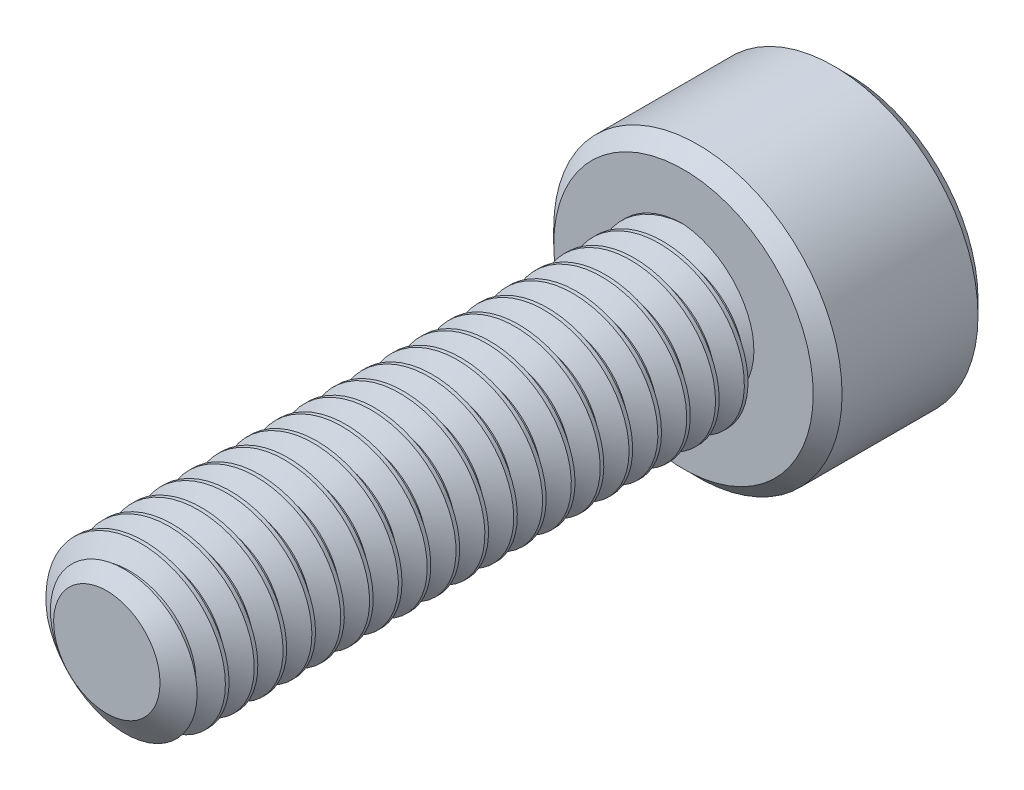
SolidWorks part; units mm, degrees
other "DetailItem1"
ref_plane "Front Plane" through (0, 0, 0) normal (0, 0, 1) x (1, 0, 0)
ref_plane "Top Plane" through (0, 0, 0) normal (0, 1, 0) x (1, 0, 0)
ref_plane "Right Plane" through (0, 0, 0) normal (1, 0, 0) x (0, 0, -1)
sketch "Sketch1" plane through (0, 0, 0) normal (0, 0, 1) x (1, 0, 0)
  circle A0 centre (0, 0) radius 2
  dimension "OD" = 4
extrude "Extrude1" add sketch "Sketch1" against normal blind 14
sketch "Sketch2" plane through (0, 0, 0) normal (0, 0, 1) x (1, 0, 0)
  circle A0 centre (0, 0) radius 2 construction
  circle A1 centre (0, 0) radius 2
curve "Helix/Spiral1" pitch 0.7 height 14.7 radius 2 centre (0, 0, 0) axis (0, 0, -1) start towards (0, 1, 0) parameters "pitch"=0.7
sketch "Sketch3" plane through (0, 0, 0) normal (1, 0, 0) x (0, 0, -1)
  line L0 (-0.6125, 2) -> (-0.35, 1.5453)
  line L1 (-0.35, 1.5453) -> (-0.2625, 1.5453)
  line L2 (-0.2625, 1.5453) -> (0, 2)
  line L3 (-0.6125, 2) -> (0, 2)
  line L4 (-0.3062, 2) -> (-0.3062, 1.5453) construction
  line L5 (-0.4812, 1.7727) -> (-0.1312, 1.7727) construction
  line L6 (0, 2) -> (0, -2) construction
  dimension "D1" = 0.0875
  dimension "D2" = 0.35
  dimension "D3" = 60
sweep "Cut-Sweep1" cut profiles "Sketch3" path "Helix/Spiral1" align with end faces yes
sketch "Sketch4" plane through (0, 0, 0) normal (1, 0, 0) x (0, 0, -1)
  line L0 (0.4962, 2) -> (0, 1.2913)
  line L1 (0, 1.2913) -> (0, 2)
  line L2 (0.4962, 2) -> (0, 2)
  line L3 (-0.6125, 2) -> (0, 2) construction
  line L4 (0, 0) -> (7.0209, 0) construction
  dimension "D1" = 55
  dimension "D2" = 0.254
revolve "Cut-Revolve1" cut sketch "Sketch4" angle 360 about L4
sketch "Sketch6" plane through (0, 0, -14) normal (0, 0, -1) x (-1, 0, 0)
  circle A0 centre (0, 0) radius 3.5
  dimension "head dia" = 7
extrude "Extrude2" add sketch "Sketch6" along normal blind 4
sketch "Sketch7" plane through (0, 0, -18) normal (0, 0, -1) x (-1, 0, 0)
  line L1 (0, 1.7321) -> (-1.5, 0.866)
  line L2 (-1.5, 0.866) -> (-1.5, -0.866)
  line L3 (-1.5, -0.866) -> (0, -1.7321)
  line L4 (0, -1.7321) -> (1.5, -0.866)
  line L5 (1.5, -0.866) -> (1.5, 0.866)
  line L6 (1.5, 0.866) -> (0, 1.7321)
  circle A0 centre (0, 0) radius 1.5 construction
  dimension "hex dia" = 3
extrude "Cut-Extrude1" cut sketch "Sketch7" against normal blind 2.25
sketch "Sketch8" plane through (0, 0, -18) normal (0, 0, -1) x (-1, 0, 0)
  circle A0 centre (0, 0) radius 1.7321
extrude "Cut-Extrude2" cut sketch "Sketch8" against normal through all draft 45
chamfer "Chamfer1" distance 0.35 angle 45 2 edges at (-3.5, 0, -18) (-3.5, 0, -14)
sketch "Sketch10" plane through (0, 0, -14) normal (0, 0, 1) x (1, 0, 0)
  circle A1 centre (0, 0) radius 2
  circle A2 centre (0, 0) radius 2
  dimension "D1" = 0
ref_plane "Plane1" through (0, 0, -22) normal (0, 0, 1) x (1, 0, 0)
extrude "partial thread" [suppressed] add sketch "Sketch10" along normal up to surface (58 mm away) separate body up to plane "Plane1"
chamfer "Chamfer2" [suppressed] distance 0.08 angle 45
combine bodies "Combine1" [suppressed] operation type add bodies to combine 107 108
sketch "Sketch9" plane through (0, 0, 0) normal (1, 0, 0) x (0, 0, -1)
  line L0 (0, 2) -> (0, -2) construction
  line L1 (1.75, 2) -> (1.75, -2) construction
  dimension "D1" = 1.75
equation "\"D3@Helix/Spiral1\" = \"screw length@Extrude1\"+\"pitch@Helix/Spiral1\""
equation "\"D1@Sketch3\" = \"pitch@Helix/Spiral1\"*.125"
equation "\"D2@Sketch3\" = \"pitch@Helix/Spiral1\"*.5"
equation "\"D1@Cut-Extrude1\" = \"hex dia@Sketch7\"*.75"
equation "\"D1@Chamfer1\" = \"head dia@Sketch6\"*.05"
equation "\"D1@Sketch9\" = \"pitch@Helix/Spiral1\"*2.5"
equation "\"D1@Chamfer2\"=\"OD@Sketch1\"*.02"
